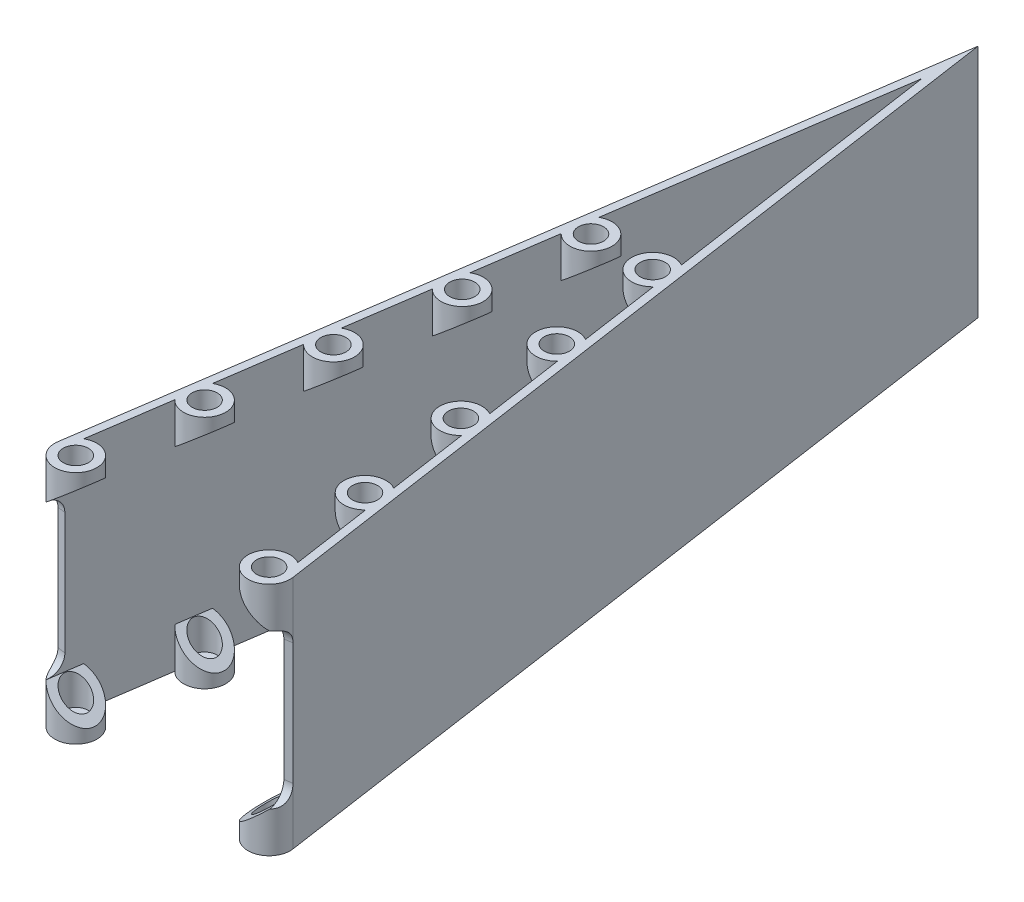
SolidWorks part; units mm, degrees
ref_plane "Front Plane" through (0, 0, 0) normal (0, 0, 1) x (1, 0, 0)
ref_plane "Top Plane" through (0, 0, 0) normal (0, 1, 0) x (1, 0, 0)
ref_plane "Right Plane" through (0, 0, 0) normal (1, 0, 0) x (0, 0, -1)
sketch "Sketch1" plane through (0, 0, 0) normal (0, 1, 0) x (1, 0, 0)
  line L0 (-13.5, 0) -> (13.5, 0) construction
  line L1 (-13.5, 0) -> (0, 92.188)
  line L2 (0, 92.188) -> (13.5, 0)
  line L3 (13.5, 0) -> (14.4894, 0.1449)
  line L4 (14.4894, 0.1449) -> (0, 99.0896)
  line L5 (0, 99.0896) -> (-14.4894, 0.1449)
  line L6 (-14.4894, 0.1449) -> (-13.5, 0)
  point P2 (0, 0)
  dimension "D1" = 90
  dimension "D2" = 90
  dimension "D4" = 1
  dimension "D3" = 100
  dimension "D5" = 27
extrude "Boss-Extrude1" add sketch "Sketch1" along normal blind 29
sketch "Sketch2" plane through (0, 0, 0) normal (0, 1, 0) x (1, 0, 0)
  line L0 (0, -1000) -> (0, 49000) construction
  line L1 (0, 92.188) -> (13.5, 0) construction
  line L2 (0, 92.188) -> (13.5, 0) construction
  line L3 (11.9169, -0.2318) -> (13.5, 0) construction
  line L4 (13.5, 0) -> (14.4894, 0.1449) construction
  line L5 (14.4894, 0.1449) -> (0, 99.0896) construction
  line L6 (14.4894, 0.1449) -> (0, 99.0896) construction
  circle A0 centre (11.9169, -0.2318) radius 2.6
  circle A1 centre (11.9169, -0.2318) radius 1.55
  circle A2 centre (9.8884, 13.6204) radius 1.55
  circle A3 centre (9.8884, 13.6204) radius 2.6
  circle A4 centre (7.8598, 27.4727) radius 1.55
  circle A5 centre (7.8598, 27.4727) radius 2.6
  circle A6 centre (5.8313, 41.3249) radius 1.55
  circle A7 centre (5.8313, 41.3249) radius 2.6
  circle A8 centre (3.8028, 55.1772) radius 1.55
  circle A9 centre (3.8028, 55.1772) radius 2.6
  circle A12 centre (-11.9169, -0.2318) radius 2.6
  circle A13 centre (-11.9169, -0.2318) radius 1.55
  circle A14 centre (-9.8884, 13.6204) radius 2.6
  circle A15 centre (-9.8884, 13.6204) radius 1.55
  circle A16 centre (-7.8598, 27.4727) radius 2.6
  circle A17 centre (-7.8598, 27.4727) radius 1.55
  circle A18 centre (-5.8313, 41.3249) radius 2.6
  circle A19 centre (-5.8313, 41.3249) radius 1.55
  circle A20 centre (-3.8028, 55.1772) radius 2.6
  circle A21 centre (-3.8028, 55.1772) radius 1.55
  dimension "D1" = 5.2
  dimension "D2" = 3.1
  dimension "D4" = 14
  dimension "D3" = 5
extrude "Boss-Extrude3" add sketch "Sketch2" along normal blind 5
sketch "Sketch4" plane through (0.2834, 0, 1.9354) normal (0.1449, 0, 0.9894) x (0.9894, 0, -0.1449)
  line L0 (9.1575, 5) -> (9.1575, 0) construction
  line L1 (14.3575, 5) -> (9.1575, 5) construction
  line L2 (13.3575, 29) -> (13.3575, 0) construction
  line L3 (9.1575, 5) -> (9.1575, 0) construction
  line L4 (14.3575, 5) -> (9.1575, 5) construction
  line L5 (13.3575, 29) -> (13.3575, 0) construction
  line L6 (13.3575, 5) -> (9.1575, 1.4758)
  line L7 (13.3575, 5) -> (9.1575, 5)
  line L8 (9.1575, 5) -> (9.1575, 1.4758)
  dimension "D1" = 40
extrude "Cut-Extrude1" cut sketch "Sketch4" against normal up to surface and the other way through all contours L7 L8 L6 region at (10.7295, 3.8253, 0.4057) up to face at (-8.5575, 4.9091, -33.751)
sketch "Sketch5" plane through (-0.2834, 0, 1.9354) normal (-0.1449, 0, 0.9894) x (0.9894, 0, 0.1449)
  line L0 (-9.1575, 0) -> (-9.1575, 5) construction
  line L1 (-9.1575, 5) -> (-14.3575, 5) construction
  line L2 (-13.3575, 29) -> (-13.3575, 0) construction
  line L3 (-9.1575, 0) -> (-9.1575, 5) construction
  line L4 (-9.1575, 5) -> (-14.3575, 5) construction
  line L5 (-13.3575, 29) -> (-13.3575, 0) construction
  line L6 (-13.3575, 5) -> (-9.1575, 1.4758)
  line L7 (-13.3575, 5) -> (-9.1575, 5)
  line L8 (-9.1575, 5) -> (-9.1575, 1.4758)
  dimension "D1" = 40
extrude "Cut-Extrude2" cut sketch "Sketch5" against normal up to surface and the other way through all contours L8 L7 L6 region at (-10.7295, 3.8253, 0.4057) up to face at (8.5575, 4.9091, -33.751)
ref_plane "Plane1" through (0, 14.5, 0) normal (0, 1, 0) x (1, 0, 0)
mirror "Mirror2" about plane through (0, 14.5, 0) normal (0, 1, 0) of "Cut-Extrude2", "Cut-Extrude1", "Boss-Extrude3"
fillet "Fillet1" radius 2 4 edges at (-13.9947, 5, -0.0724) (13.9947, 5, -0.0724) (13.9947, 24, -0.0724) (-13.9947, 24, -0.0724)
sketch "Sketch6" plane through (0, 0, 0) normal (0, -1, 0) x (1, 0, 0)
  arc A0 (-13.2031, -2.0278) -> (-14.4894, -0.1449) centre (-11.9169, 0.2318) ccw construction
  arc A1 (14.4894, -0.1449) -> (13.2031, -2.0278) centre (11.9169, 0.2318) ccw construction
  arc A2 (11.7684, -11.8245) -> (11.1745, -15.88) centre (9.8884, -13.6204) ccw construction
  arc A3 (-11.1745, -15.88) -> (-11.7684, -11.8245) centre (-9.8884, -13.6204) ccw construction
  arc A4 (-9.146, -29.7323) -> (-9.7399, -25.6768) centre (-7.8598, -27.4727) ccw construction
  arc A5 (9.7399, -25.6768) -> (9.146, -29.7323) centre (7.8598, -27.4727) ccw construction
  arc A6 (7.7114, -39.529) -> (7.1175, -43.5845) centre (5.8313, -41.3249) ccw construction
  arc A7 (-7.1175, -43.5845) -> (-7.7114, -39.529) centre (-5.8313, -41.3249) ccw construction
  arc A8 (-5.089, -57.4368) -> (-5.6829, -53.3813) centre (-3.8028, -55.1772) ccw construction
  arc A9 (5.6829, -53.3813) -> (5.089, -57.4368) centre (3.8028, -55.1772) ccw construction
  arc A10 (-13.2031, -2.0278) -> (-14.4894, -0.1449) centre (-11.9169, 0.2318) ccw
  arc A11 (14.4894, -0.1449) -> (13.2031, -2.0278) centre (11.9169, 0.2318) ccw
  arc A12 (11.7684, -11.8245) -> (11.1745, -15.88) centre (9.8884, -13.6204) ccw
  arc A13 (-11.1745, -15.88) -> (-11.7684, -11.8245) centre (-9.8884, -13.6204) ccw
  arc A14 (-9.146, -29.7323) -> (-9.7399, -25.6768) centre (-7.8598, -27.4727) ccw
  arc A15 (9.7399, -25.6768) -> (9.146, -29.7323) centre (7.8598, -27.4727) ccw
  arc A16 (7.7114, -39.529) -> (7.1175, -43.5845) centre (5.8313, -41.3249) ccw
  arc A17 (-7.1175, -43.5845) -> (-7.7114, -39.529) centre (-5.8313, -41.3249) ccw
  arc A18 (-5.089, -57.4368) -> (-5.6829, -53.3813) centre (-3.8028, -55.1772) ccw
  arc A19 (5.6829, -53.3813) -> (5.089, -57.4368) centre (3.8028, -55.1772) ccw
  circle A20 centre (3.8028, -55.1772) radius 2.6
  circle A21 centre (-3.8028, -55.1772) radius 2.6
  circle A22 centre (5.8313, -41.3249) radius 2.6
  circle A23 centre (-5.8313, -41.3249) radius 2.6
  circle A24 centre (7.8598, -27.4727) radius 2.6
  circle A25 centre (-7.8598, -27.4727) radius 2.6
  circle A26 centre (-9.8884, -13.6204) radius 2.6
  circle A27 centre (9.8884, -13.6204) radius 2.6
  circle A28 centre (11.9169, 0.2318) radius 2.6
  circle A29 centre (-11.9169, 0.2318) radius 2.6
  circle M23 centre (11.9169, 0.2318) radius 1.55
  circle M24 centre (9.8884, -13.6204) radius 1.55
  circle M25 centre (7.8598, -27.4727) radius 1.55
  circle M26 centre (5.8313, -41.3249) radius 1.55
  circle M27 centre (3.8028, -55.1772) radius 1.55
  circle M28 centre (-5.8313, -41.3249) radius 1.55
  circle M29 centre (-9.8884, -13.6204) radius 1.55
  circle M30 centre (-11.9169, 0.2318) radius 1.55
  circle M31 centre (-7.8598, -27.4727) radius 1.55
  circle M32 centre (-3.8028, -55.1772) radius 1.55
extrude "Boss-Extrude4" add sketch "Sketch6" against normal blind 1 contours M27 | M32 | M28 | M26 | M25 | M31 | M29 | M24 | M23 | M30 region at (11.9169, 0, 0.2318) region at (9.8884, 0, -13.6204) region at (7.8598, 0, -27.4727) region at (5.8313, 0, -41.3249) region at (3.8028, 0, -55.1772) region at (-5.8313, 0, -41.3249) region at (-9.8884, 0, -13.6204) region at (-11.9169, 0, 0.2318) region at (-7.8598, 0, -27.4727) region at (-3.8028, 0, -55.1772)
equation "\"D2@Sketch1\"=\"D1@Sketch1\""
